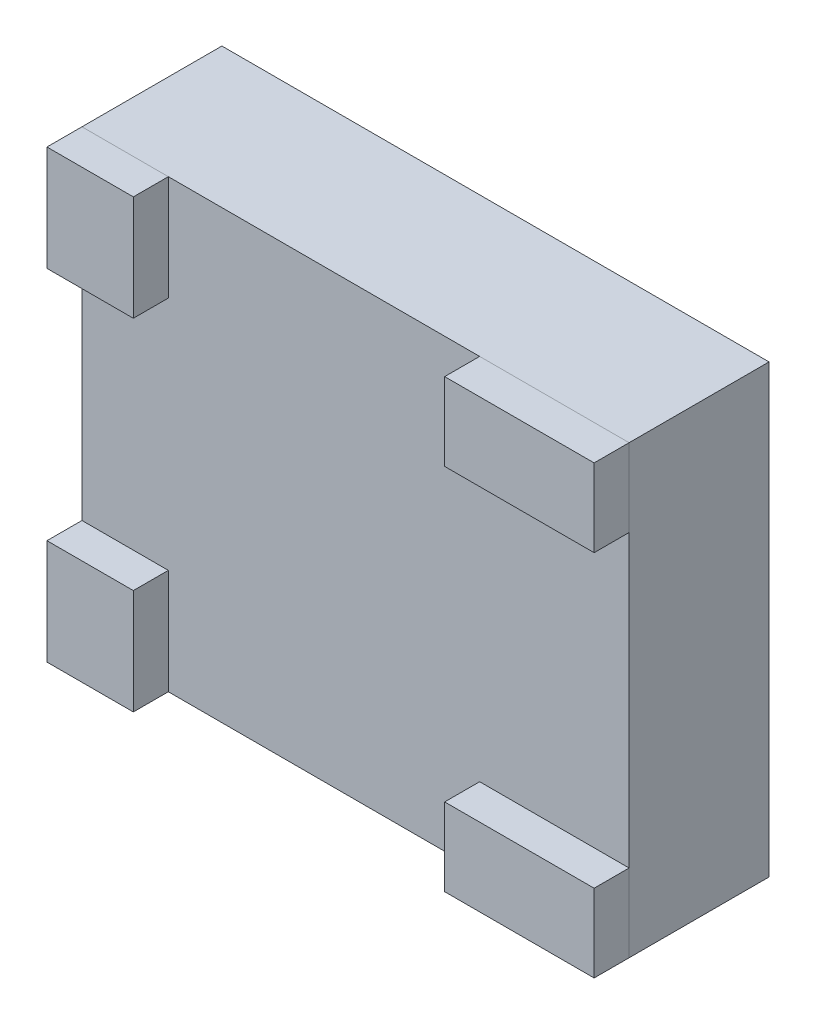
SolidWorks part; units mm, degrees
material "AISI 1020"
ref_plane "Plano superior" through (0, 0, 0) normal (0, 0, 1) x (1, 0, 0)
ref_plane "Plano frontal" through (0, 0, 0) normal (0, 1, 0) x (1, 0, 0)
ref_plane "Plano direito" through (0, 0, 0) normal (1, 0, 0) x (0, 0, -1)
other "Caixa delimitadora"
ref_plane "Default Plane" through (-78.1989, -63.755, 0) normal (0, 1, 0) x (1, 0, 0)
sketch "Esboço1" plane through (0, 0, 0) normal (0, 0, 1) x (1, 0, 0)
  line L1 (-78.1989, -63.755) -> (78.1989, -63.755)
  line L2 (-78.1989, -63.755) -> (-78.1989, 63.755)
  line L3 (-78.1989, 63.755) -> (78.1989, 63.755)
  line L4 (78.1989, -63.755) -> (78.1989, 63.755)
  line L5 (-78.1989, -63.755) -> (78.1989, 63.755) construction
  line L6 (-78.1989, 63.755) -> (78.1989, -63.755) construction
  circle A0 centre (0, 0) radius 15.125 construction
  point P0 (0, 0)
  dimension "D3" = 30.25
  dimension "D1" = 156.3979
  dimension "D2" = 127.51
extrude "Novo" add sketch "Esboço1" along normal blind 40
sketch "Esboço2" plane through (0, 0, 40) normal (0, 0, 1) x (1, 0, 0)
  line L0 (0, 0) -> (-78.1989, 0) construction
  line L1 (-78.1989, -63.755) -> (-53.5079, -63.755)
  line L2 (-78.1989, -63.755) -> (-78.1989, -33.6999)
  line L3 (-78.1989, -33.6999) -> (-53.5079, -33.6999)
  line L4 (-53.5079, -63.755) -> (-53.5079, -33.6999)
  line L5 (-78.1989, 63.755) -> (-78.1989, -63.755) construction
  line L6 (-78.1989, 33.6999) -> (-53.5079, 33.6999)
  line L7 (-53.5079, 63.755) -> (-53.5079, 33.6999)
  line L8 (-78.1989, 63.755) -> (-53.5079, 63.755)
  line L9 (-78.1989, 63.755) -> (-78.1989, 33.6999)
  line L10 (78.1989, 41.5261) -> (35.4788, 41.5261)
  line L11 (78.1989, -63.755) -> (35.4788, -63.755)
  line L12 (78.1989, -63.755) -> (78.1989, -41.5261)
  line L13 (78.1989, -41.5261) -> (35.4788, -41.5261)
  line L14 (35.4788, -63.755) -> (35.4788, -41.5261)
  line L15 (35.4788, 63.755) -> (35.4788, 41.5261)
  line L16 (78.1989, 63.755) -> (35.4788, 63.755)
  line L17 (78.1989, 63.755) -> (78.1989, 41.5261)
extrude "Ressalto-extrusão2" add sketch "Esboço2" along normal blind 10 separate body
